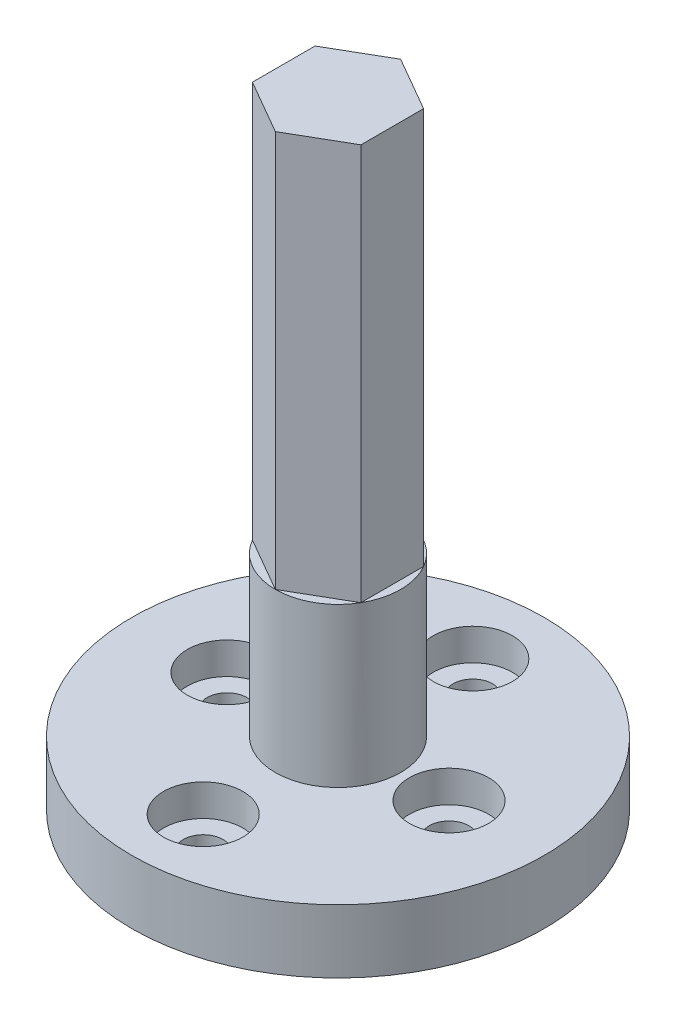
SolidWorks part; units mm, degrees
ref_plane "Alzado" through (0, 0, 0) normal (0, 0, 1) x (1, 0, 0)
ref_plane "Planta" through (0, 0, 0) normal (0, 1, 0) x (1, 0, 0)
ref_plane "Vista lateral" through (0, 0, 0) normal (1, 0, 0) x (0, 0, -1)
sketch "Croquis3" plane through (0, 0, 0) normal (0, 1, 0) x (1, 0, 0)
  circle A0 centre (0, 0) radius 13
  dimension "D1" = 26
extrude "Saliente-Extruir1" add sketch "Croquis3" along normal blind 4
sketch "Croquis4" plane through (0, 4, 0) normal (0, 1, 0) x (1, 0, 0)
  circle A0 centre (0, 0) radius 3.95
  dimension "D1" = 7.9
extrude "Saliente-Extruir2" add sketch "Croquis4" along normal blind 35
sketch "Croquis7" plane through (0, 0, 0) normal (0, -1, 0) x (1, 0, 0)
  circle A0 centre (0, 0) radius 12
  dimension "D1" = 24
sketch "Croquis8" plane through (0, 0, 0) normal (0, -1, 0) x (1, 0, 0)
  line L0 (0, -10.2812) -> (0, 10.4112) construction
  line L1 (-11.52, 0) -> (11.5297, 0) construction
  circle A1 centre (0, 8.5) radius 1.25
  circle A2 centre (0, -8.5) radius 1.25
  circle A3 centre (-7, 0) radius 1.25
  circle A4 centre (7, 0) radius 1.25
  dimension "D1" = 8.5
  dimension "D2" = 2.5
  dimension "D3" = 7
extrude "Cortar-Extruir3" cut sketch "Croquis8" against normal through all both and the other way through all
sketch "Croquis10" plane through (0, 4, 0) normal (0, 1, 0) x (1, 0, 0)
  circle A0 centre (0, -8.5) radius 1.25 construction
  circle A1 centre (0, 8.5) radius 1.25 construction
  circle A2 centre (0, -8.5) radius 1.25 construction
  circle A3 centre (0, 8.5) radius 1.25 construction
  circle A4 centre (0, 8.5) radius 2.5
  circle A5 centre (0, -8.5) radius 2.5
  circle A6 centre (7, 0) radius 1.25 construction
  circle A7 centre (-7, 0) radius 1.25 construction
  circle A8 centre (7, 0) radius 1.25
  circle A9 centre (-7, 0) radius 1.25
  circle A10 centre (-7, 0) radius 2.5
  circle A11 centre (7, 0) radius 2.5
  dimension "D1" = 5
  dimension "D2" = 5
extrude "Cortar-Extruir5" cut sketch "Croquis10" against normal blind 2 and the other way through all
sketch "Croquis9" plane through (0, 0, 0) normal (0, 1, 0) x (1, 0, 0)
  circle A0 centre (0, 0) radius 1.625
  dimension "D1" = 3.25
extrude "Cortar-Extruir4" cut sketch "Croquis9" along normal blind 3
sketch "Croquis11" plane through (0, 0, 0) normal (0, -1, 0) x (1, 0, 0)
  circle A0 centre (0, 0) radius 4
  dimension "D1" = 8
extrude "Cortar-Extruir6" cut sketch "Croquis11" against normal blind 0.5
sketch "Croquis12" plane through (0, 39, 0) normal (0, 1, 0) x (1, 0, 0)
  line L1 (0, 3.95) -> (-3.4208, 1.975)
  line L2 (-3.4208, 1.975) -> (-3.4208, -1.975)
  line L3 (-3.4208, -1.975) -> (0, -3.95)
  line L4 (0, -3.95) -> (3.4208, -1.975)
  line L5 (3.4208, -1.975) -> (3.4208, 1.975)
  line L6 (3.4208, 1.975) -> (0, 3.95)
  circle A0 centre (0, 0) radius 3.95 construction
  circle A1 centre (0, 0) radius 3.95 construction
  circle A2 centre (0, 0) radius 3.95 construction
extrude "Cortar-Extruir7" cut sketch "Croquis12" against normal blind 25 flip side to cut
